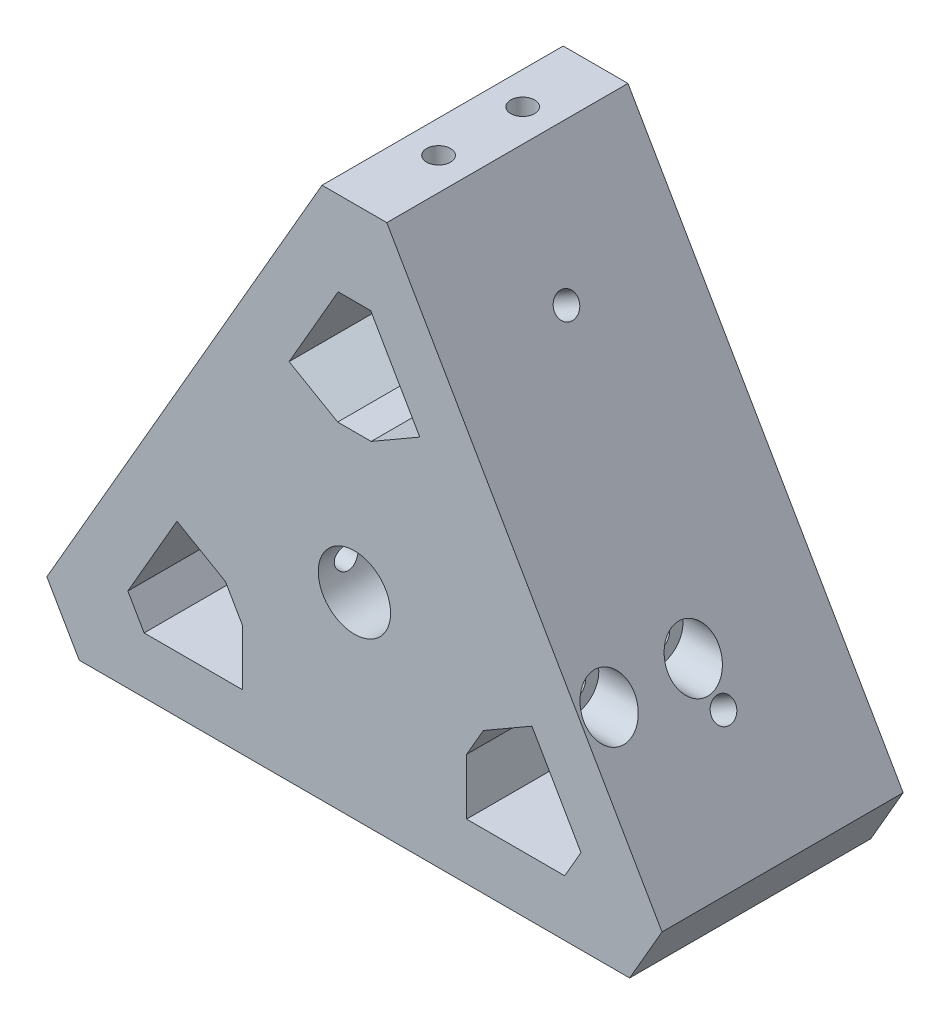
SolidWorks part; units mm, degrees
material "PLA"
ref_plane "前视基准面" through (0, 0, 0) normal (0, 0, 1) x (1, 0, 0)
ref_plane "上视基准面" through (0, 0, 0) normal (0, 1, 0) x (1, 0, 0)
ref_plane "右视基准面" through (0, 0, 0) normal (1, 0, 0) x (0, 0, -1)
other "Configuration Table"
sketch "草图1" plane through (0, 0, 0) normal (0, 0, 1) x (1, 0, 0)
  line L0 (0, 70) -> (-60.6218, -35)
  line L5 (-60.6218, -35) -> (60.6218, -35)
  line L6 (60.6218, -35) -> (0, 70)
  line L11 (0, 0) -> (0, 42.5867) construction
  line L13 (0, 0) -> (0, -35) construction
  line L14 (0, 0) -> (30.3109, 17.5) construction
  line L15 (-5.7735, 60) -> (5.7735, 60)
  line L16 (54.8483, -25) -> (49.0748, -35)
  line L17 (-49.0748, -35) -> (-54.8483, -25)
  circle A1 centre (0, 0) radius 6.45
  point P18 (0, 0)
  dimension "D5" = 3
  dimension "D1" = 12.9
  dimension "D2" = 60
  dimension "D3" = 35
  dimension "D4" = 10
extrude "凸台-拉伸1" add sketch "草图1" along normal blind 43 contours L17 L5 L16 L6 L15 L0 A1 region at (0, 58.5489, 0)
sketch "草图2" plane through (0, 0, 43) normal (0, 0, 1) x (1, 0, 0)
  line L0 (-2.9006, 44.976) -> (5.7596, 39.976)
  line L1 (5.7596, 39.976) -> (-31.7404, -24.976)
  line L2 (-5.7735, 60) -> (-54.8483, -25) construction
  line L3 (0, 0) -> (-68.0781, 39.3049) construction
  line L4 (-40.4006, -19.976) -> (-31.7404, -24.976)
  line L5 (-40.4006, -19.976) -> (-2.9006, 44.976)
  line L6 (40.4006, -19.976) -> (31.7404, -24.976)
  line L7 (31.7404, -24.976) -> (-5.7596, 39.976)
  line L8 (2.9006, 44.976) -> (-5.7596, 39.976)
  line L9 (2.9006, 44.976) -> (40.4006, -19.976)
  line L10 (-37.5, -25) -> (-37.5, -15)
  line L11 (-37.5, -15) -> (37.5, -15)
  line L12 (37.5, -25) -> (37.5, -15)
  line L13 (37.5, -25) -> (-37.5, -25)
  line L14 (-2.9904, 24.8205) -> (-11.6506, 29.8205)
  line L15 (-22.9904, -9.8205) -> (-31.6506, -4.8205)
  line L16 (22.9904, -9.8205) -> (31.6506, -4.8205)
  line L17 (2.9904, 24.8205) -> (11.6506, 29.8205)
  line L18 (-20, -15) -> (-20, -25)
  line L19 (20, -15) -> (20, -25)
  line L20 (-2.9006, 44.976) -> (2.9006, 44.976)
  line L21 (-40.4006, -19.976) -> (-37.5, -25)
  line L22 (40.4006, -19.976) -> (37.5, -25)
  line L23 (-22.9904, -9.8205) -> (-20, -15)
  line L24 (22.9904, -9.8205) -> (20, -15)
  line L25 (2.9904, 24.8205) -> (-2.9904, 24.8205)
  point P19 (0, 0)
  point P33 (0, 0)
  dimension "D1" = 75
  dimension "D2" = 10
  dimension "D3" = 10
  dimension "D5" = 40
  dimension "D4" = 3
  dimension "D6" = 3
extrude "切除-拉伸3" cut sketch "草图2" against normal through all contours L0 L8 L7 L1 | L14 L1 L7 L8 L0 L5 | L7 L17 L9 L8 L0 L1 | L1 L15 L5 L4 L10 L11 | L11 L10 L4 L1 | L18 L11 L1 L4 L10 L13 | L11 L19 L13 L12 L6 L7 | L6 L12 L11 L7 | L16 L7 L11 L12 L6 L9 | L20 L0 L8 | L4 L21 L10 | L22 L6 L12 | L7 L24 L11 | L23 L1 L11 | L25 L7 L1 region at (0, 44.4177, 43) region at (-5.239, 32.6707, 43) region at (5.239, 32.6707, 43) region at (0, 37.7591, 43) region at (-30.9131, -11.7982, 43) region at (0, 26.547, 43) region at (-38.4669, -22.2089, 43) region at (-22.9904, -13.2735, 43) region at (30.9131, -11.7982, 43) region at (-32.7003, -18.8795, 43) region at (-25.6741, -20.8724, 43) region at (22.9904, -13.2735, 43) region at (38.4669, -22.2089, 43) region at (25.6741, -20.8724, 43) region at (32.7003, -18.8795, 43)
sketch "草图3" plane through (-30.3109, 17.5, 0) normal (-0.866, 0.5, 0) x (0, 0, 1)
  line L0 (0, 0) -> (67.8776, 0) construction
  line L1 (0, 49.0748) -> (0, -49.0748) construction
  line L2 (43, 54.8483) -> (0, 54.8483) construction
  circle A0 centre (21.5, 28) radius 2.125
  circle A2 centre (21.5, -28) radius 2.125
  point P10 (21.5, 54.8483)
  dimension "D1" = 56
  dimension "D2" = 4.25
extrude "切除-拉伸4" cut sketch "草图3" against normal blind 15
pattern_circular "阵列(圆周)1" count 3 over 360 about axis through (0, 0, 43) along (0, 0, -1) of "切除-拉伸4"
sketch "草图4" plane through (0, -35, 0) normal (0, -1, 0) x (1, 0, 0)
  line L0 (-49.0748, 0) -> (49.0748, 0) construction
  circle A0 centre (0, 13) radius 2.125
  circle A1 centre (0, 28) radius 2.125
  dimension "D1" = 13
  dimension "D2" = 15
  dimension "D3" = 4.25
extrude "切除-拉伸5" cut sketch "草图4" against normal through all
ref_plane "基准面1" through (49.0748, 0, 0) normal (-1, 0, 0) x (0, 0, -1)
sketch "草图6" plane through (49.0748, 0, 0) normal (-1, 0, 0) x (0, 0, -1)
  line L5 (0, 25) -> (0, -60) construction
  line L6 (-21.5, 35) -> (-21.5, -35) construction
  line L7 (-43, 35) -> (0, 35) construction
  circle A0 centre (-23, 0) radius 2.15
  circle A1 centre (-38, 0) radius 2.15
  point P7 (-21.5, 0)
  dimension "D1" = 15
  dimension "D2" = 70
  dimension "D3" = 4.3
  dimension "D4" = 23
extrude "切除-拉伸7" cut sketch "草图6" along normal through all
sketch "草图7" plane through (49.0748, 0, 0) normal (-1, 0, 0) x (0, 0, -1)
  circle A0 centre (-38, 0) radius 4.5
  circle A1 centre (-23, 0) radius 4.5
  dimension "D1" = 9
  dimension "D2" = 9
extrude "切除-拉伸8" cut sketch "草图7" along normal blind 15
